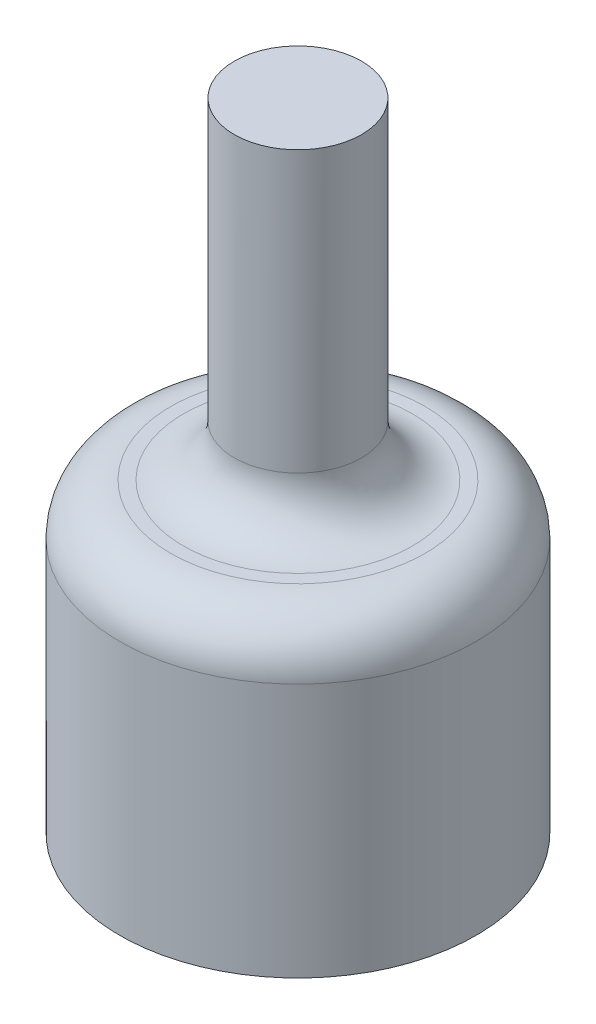
SolidWorks part; units mm, degrees
ref_plane "Front Plane" through (0, 0, 0) normal (0, 0, 1) x (1, 0, 0)
ref_plane "Top Plane" through (0, 0, 0) normal (0, 1, 0) x (1, 0, 0)
ref_plane "Right Plane" through (0, 0, 0) normal (1, 0, 0) x (0, 0, -1)
sketch "Sketch1" plane through (0, 0, 0) normal (0, 1, 0) x (1, 0, 0)
  line L0 (0, -7.5) -> (0, 7.5)
  line L1 (-7.5, 0) -> (7.5, 0)
  circle A0 centre (0, 0) radius 12.5
  circle A1 centre (-7.5, 0) radius 2
  circle A2 centre (0, 7.5) radius 2
  circle A3 centre (7.5, 0) radius 2
  circle A4 centre (0, -7.5) radius 2
  point P6 (0, 0)
  point P9 (0, 0)
  dimension "D1" = 25
  dimension "D4" = 4
  dimension "D5" = 4
  dimension "D6" = 4
  dimension "D7" = 4
  dimension "D2" = 15
  dimension "D3" = 15
extrude "Boss-Extrude1" add sketch "Sketch1" along normal blind 5 contours A0 A4 A1 A2 A3 region at (-12.1464, 0, 0)
sketch "Sketch2" plane through (0, 5, 0) normal (0, 1, 0) x (1, 0, 0)
  circle A0 centre (0, 0) radius 2.5
  dimension "D1" = 5
extrude "Boss-Extrude2" add sketch "Sketch2" along normal blind 15
sketch "Sketch3" plane through (0, 0, 0) normal (0, -1, 0) x (1, 0, 0)
  circle A0 centre (0, 0) radius 5
  dimension "D1" = 10
extrude "Cut-Extrude1" cut sketch "Sketch3" against normal blind 2
sketch "Sketch4" plane through (0, 5, 0) normal (0, 1, 0) x (1, 0, 0)
  circle A0 centre (0, 0) radius 12.5
  dimension "D1" = 25
extrude "Cut-Extrude2" cut sketch "Sketch4" against normal through all
sketch "Sketch5" plane through (0, 5, 0) normal (0, -1, 0) x (1, 0, 0)
  line L0 (0, -2.95) -> (0, 1.75)
  line L1 (-2.3749, 1.75) -> (2.3749, 1.75)
  circle A0 centre (0, 0) radius 7
  circle A1 centre (0, 0) radius 2.95
  point P9 (0, 1.75)
  circle M2 centre (0, 0) radius 2.5
  dimension "D1" = 14
  dimension "D2" = 5.9
  dimension "D3" = 4.7
extrude "Boss-Extrude3" add sketch "Sketch5" along normal blind 10 contours A0 A1 | L1 M2 | L1 A1 M2 region at (0, 5, 2.901) region at (0, 5, 2.0542) region at (-6.802, 5, 0)
extrude "Boss-Extrude4" add sketch "Sketch5<3>" against normal blind 2 contours A0 A1 | L1 M2 | L1 A1 M2 | L0 A1 L1 M2 | L1 L0 M2 | L1 L0 M2 | L1 A1 L0 M2 region at (-2.5834, 5, -1.3054) region at (0.0555, 5, -2.725) region at (-1.1, 5, -0.2133) region at (1.1, 5, -0.2133) region at (0, 5, 2.901) region at (0, 5, 2.0542) region at (-6.802, 5, 0)
sketch "Sketch5<3>" plane through (0, 5, 0) normal (0, -1, 0) x (1, 0, 0) same geometry as "Sketch5"
fillet "Fillet1" radius 2 1 edges at (0, 7, -2.5)
fillet "Fillet2" radius 2 1 edges at (0, 7, -7)
